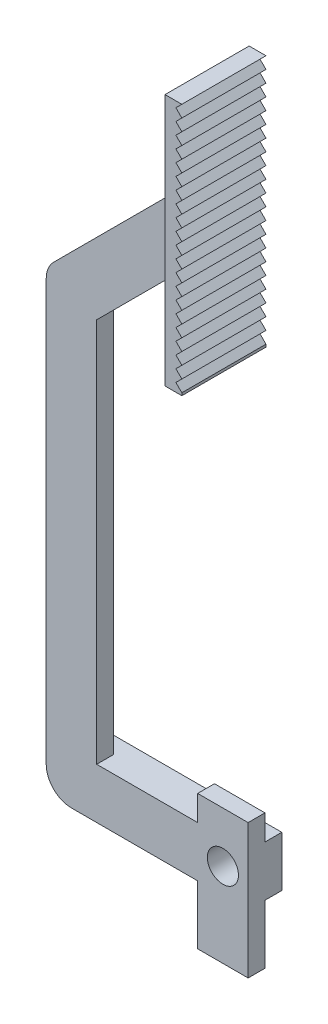
SolidWorks part; units mm, degrees
ref_plane "前视基准面" through (0, 0, 0) normal (0, 0, 1) x (1, 0, 0)
ref_plane "上视基准面" through (0, 0, 0) normal (0, 1, 0) x (1, 0, 0)
ref_plane "右视基准面" through (0, 0, 0) normal (1, 0, 0) x (0, 0, -1)
sketch "草图1" plane through (0, 0, 0) normal (0, 0, 1) x (1, 0, 0)
  line L0 (16, 6) -> (15, 6)
  line L2 (0, 0) -> (28, 0) construction
  line L3 (3, 3) -> (15, 3)
  line L4 (0, -3) -> (15, -3)
  line L5 (0, 0) -> (0, 40) construction
  line L6 (0, -55) -> (0, 55) construction
  line L9 (0, 0) -> (0, 50) construction
  line L13 (-3, 0) -> (-3, 50)
  line L14 (15, -3) -> (15, -10)
  line L15 (16, 6) -> (20, 6)
  line L17 (16, -10) -> (20, -10)
  line L19 (21, 3) -> (21, 6)
  line L20 (21, 3) -> (21, -3)
  line L21 (3, 3) -> (3, 48.7574)
  line L22 (20, 6) -> (21, 6)
  line L23 (15, 6) -> (15, 3)
  line L24 (15, -10) -> (20.5, -10)
  line L25 (20.5, -10) -> (21, -10)
  line L26 (21, -10) -> (21, -3)
  line L27 (0, 50) -> (13, 63) construction
  line L28 (-2.1213, 52.1213) -> (10.8787, 65.1213)
  line L29 (3, 48.7574) -> (15.1213, 60.8787)
  line L30 (10.8787, 65.1213) -> (15.1213, 69.364)
  line L31 (15.1213, 69.364) -> (15.1213, 60.8787)
  line L32 (3, 3) -> (-3, 3)
  arc A0 (-3, 0) -> (0, -3) centre (0, 0) ccw
  arc A2 (-3, 0) -> (0, -3) centre (0, 0) ccw
  circle A7 centre (18, 0) radius 1.85
  arc A8 (-3, 0) -> (0, -3) centre (0, 0) ccw
  arc A10 (-2.1213, 52.1213) -> (-3, 50) centre (0, 50) ccw
  arc A12 (-2.1213, 52.1213) -> (-3, 50) centre (0, 50) ccw
  point P2 (14, 0)
  point P7 (0, 25)
  point P10 (0, 20)
  point P25 (6.5, 56.5)
  dimension "D1" = 13
  dimension "D2" = 13
extrude "凸台-拉伸1" add sketch "草图1" along normal mid plane 4 contours A0 L4 L17 L15 L3 region at (11.4311, -0.9801, 0)
sketch "草图4" plane through (0, 0, 2) normal (0, 0, 1) x (1, 0, 0)
  line L1 (15, 3) -> (21, 3)
  line L2 (15, 3) -> (15, 6)
  line L3 (15, 6) -> (21, 6)
  line L4 (21, 3) -> (21, 6)
  line L5 (15, -3) -> (21, -3)
  line L6 (15, -3) -> (15, -10)
  line L7 (15, -10) -> (21, -10)
  line L8 (21, -3) -> (21, -10)
extrude "切除-拉伸2" cut sketch "草图4" along normal blind 2 from surface starting at face at (19.85, 0, -2)
extrude "凸台-拉伸2" add sketch "草图1<3>" along normal blind 2 contours L28 A10 L13 L32 L21 L29 L31 L30 region at (2.3175, 36.2665, 0)
sketch "草图1<3>" plane through (0, 0, 0) normal (0, 0, 1) x (1, 0, 0) same geometry as "草图1"
sketch "草图5" plane through (15.1213, 0, 0) normal (1, 0, 0) x (0, 0, -1)
  line L1 (-6, 50) -> (4, 50)
  line L2 (-6, 50) -> (-6, 80)
  line L3 (-6, 80) -> (4, 80)
  line L4 (4, 50) -> (4, 80)
  line L5 (-6, 50) -> (4, 80) construction
  line L6 (-6, 80) -> (4, 50) construction
  point P0 (-1, 65)
extrude "凸台-拉伸3" add sketch "草图5" along normal blind 2
sketch "草图6" plane through (0, 0, 6) normal (0, 0, 1) x (1, 0, 0)
  line L0 (17.1213, 80) -> (16.4142, 79.2929)
  line L1 (16.4142, 79.2929) -> (17.1213, 78.5858)
  line L2 (17.1213, 80) -> (17.1213, 50) construction
  line L3 (17.1213, 78.5858) -> (17.1213, 80)
extrude "切除-拉伸3" cut sketch "草图6" against normal blind 10
pattern_linear "阵列(线性)1" count 21 spacing 1.414 along (0, -1, 0) of "切除-拉伸3"
